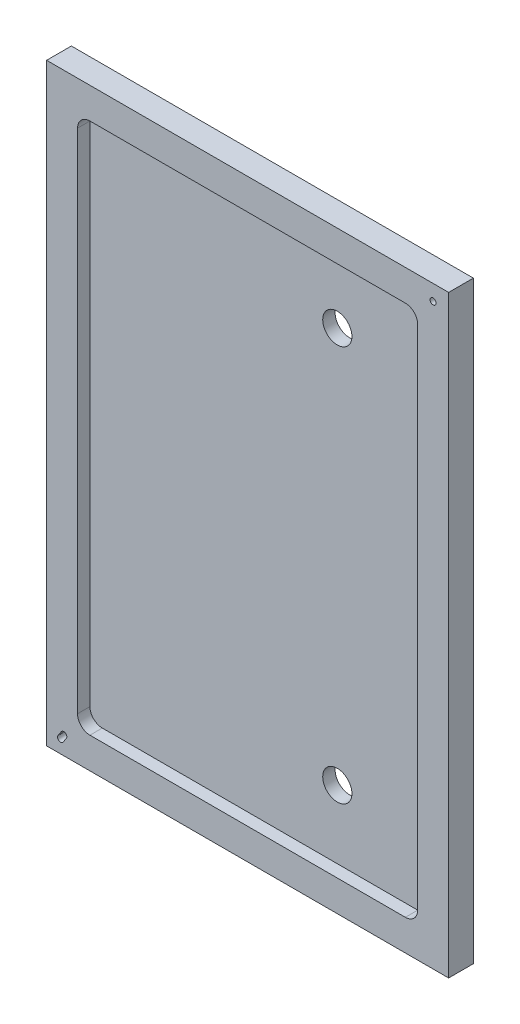
SolidWorks part; units mm, degrees
ref_plane "Front Plane" through (0, 0, 0) normal (0, 0, 1) x (1, 0, 0)
ref_plane "Top Plane" through (0, 0, 0) normal (0, 1, 0) x (1, 0, 0)
ref_plane "Right Plane" through (0, 0, 0) normal (1, 0, 0) x (0, 0, -1)
sketch "Sketch1" plane through (0, 0, 0) normal (0, 0, 1) x (1, 0, 0)
  line L1 (103.1875, -152.4) -> (-103.1875, -152.4)
  line L2 (103.1875, -152.4) -> (103.1875, 152.4)
  line L3 (103.1875, 152.4) -> (-103.1875, 152.4)
  line L4 (-103.1875, -152.4) -> (-103.1875, 152.4)
  line L5 (103.1875, -152.4) -> (-103.1875, 152.4) construction
  line L6 (103.1875, 152.4) -> (-103.1875, -152.4) construction
  point P0 (0, 0)
  dimension "D1" = 304.8
  dimension "D2" = 206.375
extrude "Boss-Extrude1" add sketch "Sketch1" along normal blind 12.7
sketch "Sketch2" plane through (0, 0, 12.7) normal (0, 0, 1) x (1, 0, 0)
  line L0 (-103.1875, 152.4) -> (-103.1875, -152.4) construction
  line L1 (80.9625, -136.525) -> (-80.9625, -136.525)
  line L2 (87.3125, -130.175) -> (87.3125, 130.175)
  line L3 (80.9625, 136.525) -> (-80.9625, 136.525)
  line L4 (-87.3125, -130.175) -> (-87.3125, 130.175)
  line L5 (87.3125, -136.525) -> (-87.3125, 136.525) construction
  line L6 (87.3125, 136.525) -> (-87.3125, -136.525) construction
  line L7 (103.1875, 152.4) -> (-103.1875, 152.4) construction
  arc A0 (-80.9625, -136.525) -> (-87.3125, -130.175) centre (-80.9625, -130.175) cw
  arc A1 (80.9625, -136.525) -> (87.3125, -130.175) centre (80.9625, -130.175) ccw
  arc A2 (87.3125, 130.175) -> (80.9625, 136.525) centre (80.9625, 130.175) ccw
  arc A3 (-80.9625, 136.525) -> (-87.3125, 130.175) centre (-80.9625, 130.175) ccw
  point P0 (0, 0)
  dimension "D3" = 6.35
  dimension "D1" = 15.875
  dimension "D2" = 15.875
extrude "Cut-Extrude1" cut sketch "Sketch2" against normal blind 6.35
sketch "Sketch4" plane through (0, 0, 0) normal (0, 0, -1) x (-1, 0, 0)
  line L0 (103.1875, -152.4) -> (-103.1875, -152.4) construction
  line L1 (-103.1875, -152.4) -> (-103.1875, 152.4) construction
  line L2 (0, 0) -> (-117.2439, 0) construction
  circle A0 centre (-39.6875, -101.6) radius 7.5
  circle A1 centre (-39.6875, 101.6) radius 7.5
  dimension "D1" = 15
  dimension "D2" = 50.8
  dimension "D3" = 63.5
  dimension "D4" = 0
extrude "Cut-Extrude3" cut sketch "Sketch4" against normal through all
hole_wizard "Ø3.1 (3.1) Diameter Hole1" positions "Sketch7" profile "Sketch8" hole size "Ø3.1" standard "ANSI Metric"
sketch "Sketch7" plane through (0, 0, 12.7) normal (0, 0, 1) x (1, 0, 0)
  line L0 (103.1875, -152.4) -> (103.1875, 152.4) construction
  line L1 (103.1875, 152.4) -> (-103.1875, 152.4) construction
  point P0 (95.1875, 144.4)
  dimension "D1" = 8
  dimension "D2" = 8
sketch "Sketch8" plane through (95.1875, 144.4, 12.7) normal (1, 0, 0) x (0, -1, 0)
  line L0 (0, 0) -> (0, 5.9313)
  line L1 (0, 5.9313) -> (1.55, 5)
  line L2 (1.55, 5) -> (1.55, 0)
  line L5 (1.55, 0) -> (0, 0)
  line L10 (0, 5.9313) -> (-1.55, 5) construction
  line L11 (0, -6.35) -> (0, 107.95) construction
  dimension "Hole Dia." = 3.1
  dimension "Hole Depth" = 5
  dimension "Drill Angle" = 118
sketch "Sketch9" plane through (0, 0, 12.7) normal (0, 0, 1) x (1, 0, 0)
  line L0 (-96.0154, -145.6508) -> (-94.3596, -143.1492) construction
  line L1 (-97.3079, -144.7953) -> (-95.6521, -142.2937)
  line L2 (-94.7229, -146.5063) -> (-93.0671, -144.0047)
  line L3 (-103.1875, -152.4) -> (103.1875, -152.4) construction
  line L4 (-103.1875, 152.4) -> (-103.1875, -152.4) construction
  arc A0 (-97.3079, -144.7953) -> (-94.7229, -146.5063) centre (-96.0154, -145.6508) ccw
  arc A1 (-93.0671, -144.0047) -> (-95.6521, -142.2937) centre (-94.3596, -143.1492) ccw
  point P4 (-95.1875, -144.4)
  dimension "D1" = 3.1
  dimension "D2" = 8
  dimension "D3" = 8
  dimension "D4" = 3
  dimension "D5" = 56.5
extrude "Cut-Extrude4" cut sketch "Sketch9" against normal blind 5
hole_wizard "M4x0.7 Tapped Hole1" positions "Sketch10" profile "Sketch11" tap size "M4x0.7" standard "ANSI Metric"
sketch "Sketch10" plane through (0, 0, 0) normal (0, 0, -1) x (-1, 0, 0)
  line L0 (103.1875, 152.4) -> (103.1875, -152.4) construction
  line L1 (-103.1875, 152.4) -> (103.1875, 152.4) construction
  point P0 (95.1875, -113.6)
  point P2 (95.1875, 113.6)
  dimension "D1" = 8
  dimension "D2" = 38.8
  dimension "D3" = 266
sketch "Sketch11" plane through (-95.1875, -113.6, 0) normal (1, 0, 0) x (0, 1, 0)
  line L0 (0, 0) -> (0, 6.3914)
  line L1 (0, 6.3914) -> (1.65, 5.4)
  line L2 (1.65, 5.4) -> (1.65, 0)
  line L5 (1.65, 0) -> (0, 0)
  line L10 (0, 6.3914) -> (-1.65, 5.4) construction
  line L11 (0, -6.35) -> (0, 107.95) construction
  dimension "Tap Drill Dia." = 3.3
  dimension "Tap Drill Depth" = 5.4
  dimension "Drill Angle" = 118
cosmetic thread "Hole Thread1" parameters "D1"=3, "D2"=4
cosmetic thread "Hole Thread2" parameters "D1"=3, "D2"=4
